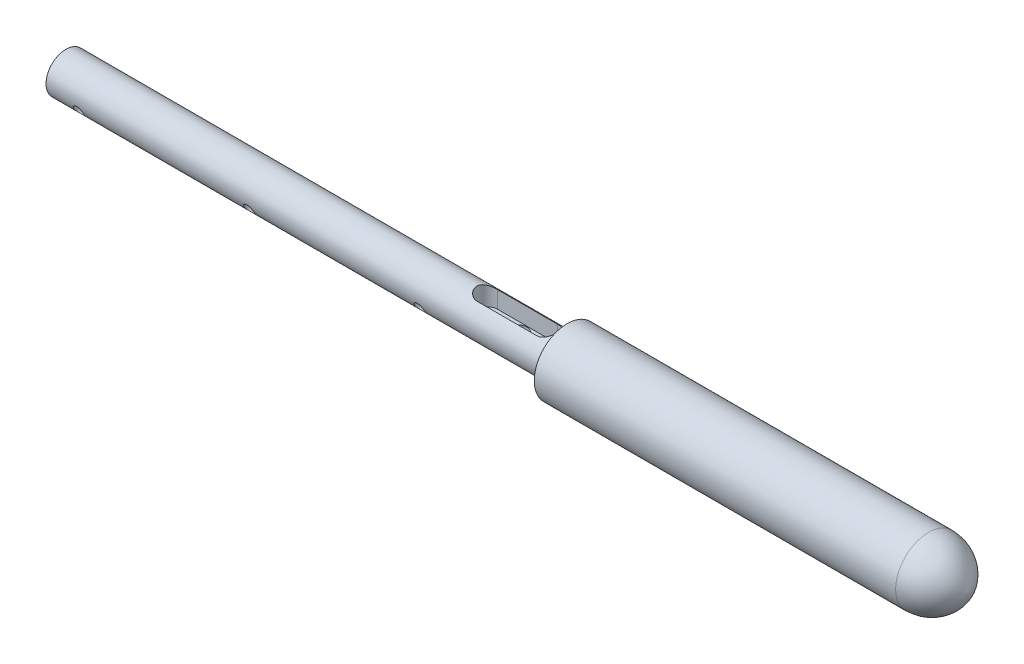
SolidWorks part; units mm, degrees
ref_plane "Front Plane" through (0, 0, 0) normal (0, 0, 1) x (1, 0, 0)
ref_plane "Top Plane" through (0, 0, 0) normal (0, 1, 0) x (1, 0, 0)
ref_plane "Right Plane" through (0, 0, 0) normal (1, 0, 0) x (0, 0, -1)
sketch "Sketch1" plane through (0, 0, 0) normal (1, 0, 0) x (0, 0, -1)
  circle A0 centre (0, 0) radius 3.175
  dimension "D1" = 6.35
extrude "Boss-Extrude1" add sketch "Sketch1" along normal blind 127
sketch "Sketch2" plane through (0, 0, 0) normal (0, 0, 1) x (1, 0, 0)
  line L0 (142.875, 0) -> (79.375, 0)
  line L2 (79.375, 0) -> (79.375, 5.207)
  line L3 (79.375, 5.207) -> (136.6287, 5.207)
  line L4 (0, 3.175) -> (0, -3.175) construction
  arc A0 (136.6287, 5.207) -> (142.875, 0) centre (136.6287, -1.143) cw
  dimension "D1" = 6.35
  dimension "D2" = 5.207
  dimension "D3" = 63.5
  dimension "D4" = 79.375
ref_axis "Axis1" through (127, 0, 0) along (-1, 0, 0)
revolve "Revolve1" add sketch "Sketch2" angle 360 about axis through (127, 0, 0) along (-1, 0, 0)
sketch "Sketch3" plane through (0, 0, 0) normal (-1, 0, 0) x (0, 0, 1)
  line L1 (-0.7938, 3.175) -> (0.7937, 3.175)
  line L2 (-0.7938, 3.175) -> (-0.7937, -3.175)
  line L3 (-0.7937, -3.175) -> (0.7938, -3.175)
  line L4 (0.7937, 3.175) -> (0.7938, -3.175)
  dimension "D1" = 1.5875
  dimension "D2" = 0.7937
  dimension "D3" = 6.35
  dimension "D4" = 3.175
sketch "Sketch4" plane through (0, 0, 0) normal (0, 1, 0) x (1, 0, 0)
  line L1 (76.2, 1.6718) -> (66.675, 1.6718)
  line L2 (0, 3.175) -> (0, -3.175) construction
  line L3 (76.2, -1.5962) -> (66.675, -1.5962)
  arc A0 (66.675, 1.6718) -> (66.675, -1.5962) centre (66.675, 0.0378) ccw
  arc A1 (76.2, 1.6718) -> (76.2, -1.5962) centre (76.2, 0.0378) cw
  dimension "D2" = 9.525
  dimension "D1" = 3.2679
  dimension "D3" = 66.675
extrude "Cut-Extrude2" cut sketch "Sketch4" along normal blind 3.175
hole_wizard "#32 (0.116) Diameter Hole1" positions "Sketch6" profile "Sketch5" hole size "#32" standard "Ansi Inch"
sketch "Sketch6" plane through (0, 0, 0) normal (0, 1, 0) x (-1, 0, 0)
  line L0 (-76.2, -1.6718) -> (-66.675, -1.6718) construction
  arc A0 (-66.675, -1.6718) -> (-66.675, 1.5962) centre (-66.675, -0.0378) ccw construction
  point P0 (-71.4375, -0.0843)
  dimension "D1" = 1.5875
  dimension "D2" = 4.7625
sketch "Sketch5" plane through (71.4375, 0, -0.0843) normal (1, 0, 0) x (0, 0, 1)
  line L0 (0, 0) -> (0, 26.2852)
  line L1 (0, 26.2852) -> (1.4732, 25.4)
  line L2 (1.4732, 25.4) -> (1.4732, 0)
  line L5 (1.4732, 0) -> (0, 0)
  line L10 (0, 26.2852) -> (-1.4732, 25.4) construction
  line L11 (0, -6.35) -> (0, 107.95) construction
  dimension "Hole Dia." = 2.9464
  dimension "Hole Depth" = 25.4
  dimension "Drill Angle" = 118
sketch "Sketch7" plane through (0, 0, 0) normal (0, 0, 1) x (1, 0, 0)
  line L1 (0, 3.175) -> (0, -3.175) construction
  line L2 (127, 0) -> (0, 0) construction
  circle A0 centre (4.7625, -1.5875) radius 0.7937
  dimension "D1" = 1.5875
  dimension "D2" = 4.7625
  dimension "D3" = 1.5875
extrude "Cut-Extrude3" cut sketch "Sketch7" against normal blind 5.08 and the other way blind 5.08
ref_axis "Axis2" through (71.4375, -3.175, -0.0843) along (0, 1, 0)
sketch "Sketch9" plane through (0, 0, 0) normal (0, 0, 1) x (1, 0, 0)
  line L0 (71.4375, 4.9906) -> (71.4375, -10.9572) construction
  line L1 (71.4375, -3.175) -> (71.4375, 0) construction
ref_point "Point1"
sketch "Sketch10" plane through (0, 0, 0) normal (0, 1, 0) x (1, 0, 0)
  line L1 (0, 0.7937) -> (9.525, 0.7937)
  line L2 (0, 0.7937) -> (0, -0.7937)
  line L3 (0, -0.7937) -> (9.525, -0.7937)
  line L4 (9.525, 0.7937) -> (9.525, -0.7937)
  line L5 (127, 0) -> (0, 0) construction
  line L6 (0, 3.175) -> (0, -3.175) construction
  line L8 (28.575, 0.7938) -> (34.925, 0.7938)
  line L9 (28.575, 0.7938) -> (28.575, -0.7937)
  line L10 (28.575, -0.7937) -> (34.925, -0.7937)
  line L11 (34.925, 0.7938) -> (34.925, -0.7937)
  line L12 (53.975, 0.7938) -> (63.5, 0.7938)
  line L13 (53.975, 0.7938) -> (53.975, -0.7937)
  line L14 (53.975, -0.7937) -> (63.5, -0.7937)
  line L15 (63.5, 0.7938) -> (63.5, -0.7937)
  dimension "D1" = 1.5875
  dimension "D2" = 6.35
  dimension "D3" = 9.525
  dimension "D4" = 0.7937
  dimension "D5" = 9.525
  dimension "D6" = 19.05
  dimension "D7" = 19.05
  dimension "D8" = 1.5875
  dimension "D9" = 1.5875
  dimension "D10" = 0.7938
  dimension "D11" = 0.7938
extrude "Cut-Extrude4" cut sketch "Sketch10" against normal blind 5.715
pattern_linear "LPattern1" count 3 spacing 26.9875 along (1, 0, 0) of "Cut-Extrude3"
